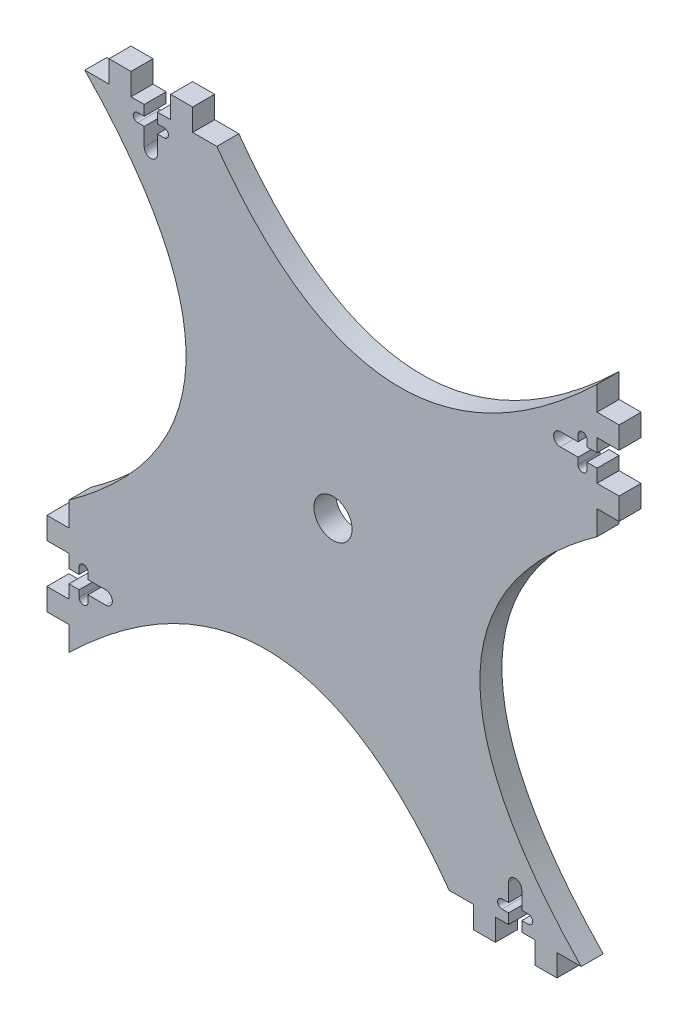
SolidWorks part; units mm, degrees
ref_plane "Front Plane" through (0, 0, 0) normal (0, 0, 1) x (1, 0, 0)
ref_plane "Top Plane" through (0, 0, 0) normal (0, 1, 0) x (1, 0, 0)
ref_plane "Right Plane" through (0, 0, 0) normal (1, 0, 0) x (0, 0, -1)
sketch "Sketch1" plane through (0, 0, 0) normal (0, 0, 1) x (1, 0, 0)
  line L0 (-16.6747, 52.5) -> (-46.6747, 52.5)
  line L1 (69.715, 48.8897) -> (69.715, 18.8897)
  line L2 (66.1047, -67.5) -> (36.1047, -67.5)
  line L3 (-50.285, -33.8897) -> (-50.285, -63.8897)
  line L9 (-31.6747, 52.5) -> (51.1047, -67.5) construction
  line L10 (-50.285, -48.8897) -> (69.715, 33.8897) construction
  circle A0 centre (9.715, -7.5) radius 35 construction
  circle A1 centre (9.715, -7.5) radius 4.337
  spline S0 degree 2 poles (69.715, 48.8897) (20.2003, 1.1367) (-16.6747, 52.5) knots 0 0 0 1 1 1
  spline S1 degree 2 poles (-46.6747, 52.5) (1.0783, 2.9853) (-50.285, -33.8897) knots 0 0 0 1 1 1
  spline S2 degree 2 poles (-50.285, -63.8897) (-0.7703, -16.1367) (36.1047, -67.5) knots 0 0 0 1 1 1
  spline S3 degree 2 poles (66.1047, -67.5) (18.3517, -17.9853) (69.715, 18.8897) knots 0 0 0 1 1 1
  dimension "D2" = 70
  dimension "D1" = 30
extrude "Boss-Extrude1" add sketch "Sketch1" along normal blind 5
sketch "Sketch2" plane through (0, 0, 5) normal (0, 0, 1) x (1, 0, 0)
  line L0 (-31.6747, 52.5) -> (-31.6747, 44.1355) construction
  line L1 (-16.6747, 52.5) -> (-46.6747, 52.5) construction
  line L2 (-33.1747, 52.5) -> (-33.1747, 44.1355)
  line L3 (-30.1747, 52.5) -> (-30.1747, 44.1355)
  line L4 (-34.6747, 49.181) -> (-28.6747, 49.181) construction
  line L5 (-34.6747, 50.181) -> (-28.6747, 50.181)
  line L6 (-34.6747, 48.181) -> (-28.6747, 48.181)
  line L23 (69.715, 35.3897) -> (61.3505, 35.3897)
  line L24 (69.715, 32.3897) -> (61.3505, 32.3897)
  line L25 (69.715, 33.8897) -> (61.3505, 33.8897) construction
  line L26 (66.396, 36.8897) -> (66.396, 30.8897) construction
  line L27 (69.715, 18.8897) -> (69.715, 48.8897)
  line L28 (36.1047, -67.5) -> (66.1047, -67.5)
  line L29 (-50.285, -33.8897) -> (-50.285, -63.8897)
  line L30 (-16.6747, 52.5) -> (-46.6747, 52.5)
  line L31 (69.715, 18.8897) -> (69.715, 48.8897)
  line L32 (36.1047, -67.5) -> (66.1047, -67.5)
  line L33 (-50.285, -33.8897) -> (-50.285, -63.8897)
  line L34 (-16.6747, 52.5) -> (-46.6747, 52.5)
  line L35 (69.715, 18.8897) -> (69.715, 48.8897)
  line L36 (36.1047, -67.5) -> (66.1047, -67.5)
  line L37 (-50.285, -33.8897) -> (-50.285, -63.8897)
  line L38 (-16.6747, 52.5) -> (-46.6747, 52.5)
  line L39 (69.715, 18.8897) -> (69.715, 48.8897)
  line L40 (36.1047, -67.5) -> (66.1047, -67.5)
  line L41 (-50.285, -33.8897) -> (-50.285, -63.8897)
  line L42 (-16.6747, 52.5) -> (-46.6747, 52.5)
  line L43 (67.396, 36.8897) -> (67.396, 30.8897)
  line L44 (65.396, 36.8897) -> (65.396, 30.8897)
  line L45 (52.6047, -67.5) -> (52.6047, -59.1355)
  line L46 (49.6047, -67.5) -> (49.6047, -59.1355)
  line L47 (51.1047, -67.5) -> (51.1047, -59.1355) construction
  line L48 (54.1047, -64.181) -> (48.1047, -64.181) construction
  line L49 (54.1047, -65.181) -> (48.1047, -65.181)
  line L50 (54.1047, -63.181) -> (48.1047, -63.181)
  line L51 (-50.285, -50.3897) -> (-41.9205, -50.3897)
  line L52 (-50.285, -47.3897) -> (-41.9205, -47.3897)
  line L53 (-50.285, -48.8897) -> (-41.9205, -48.8897) construction
  line L54 (-46.966, -51.8897) -> (-46.966, -45.8897) construction
  line L55 (-47.966, -51.8897) -> (-47.966, -45.8897)
  line L56 (-45.966, -51.8897) -> (-45.966, -45.8897)
  arc A0 (-33.1747, 52.5) -> (-30.1747, 52.5) centre (-31.6747, 52.5) cw
  arc A1 (-33.1747, 44.1355) -> (-30.1747, 44.1355) centre (-31.6747, 44.1355) ccw
  arc A2 (-34.6747, 50.181) -> (-34.6747, 48.181) centre (-34.6747, 49.181) ccw
  arc A3 (-28.6747, 48.181) -> (-28.6747, 50.181) centre (-28.6747, 49.181) ccw
  arc A4 (61.3505, 35.3897) -> (61.3505, 32.3897) centre (61.3505, 33.8897) ccw
  arc A5 (67.396, 36.8897) -> (65.396, 36.8897) centre (66.396, 36.8897) ccw
  arc A6 (65.396, 30.8897) -> (67.396, 30.8897) centre (66.396, 30.8897) ccw
  arc A7 (52.6047, -59.1355) -> (49.6047, -59.1355) centre (51.1047, -59.1355) ccw
  arc A8 (54.1047, -65.181) -> (54.1047, -63.181) centre (54.1047, -64.181) ccw
  arc A9 (48.1047, -63.181) -> (48.1047, -65.181) centre (48.1047, -64.181) ccw
  arc A10 (-41.9205, -50.3897) -> (-41.9205, -47.3897) centre (-41.9205, -48.8897) ccw
  arc A11 (-47.966, -51.8897) -> (-45.966, -51.8897) centre (-46.966, -51.8897) ccw
  arc A12 (-45.966, -45.8897) -> (-47.966, -45.8897) centre (-46.966, -45.8897) ccw
  parabola Q24 (66.1047, -67.5) -> (69.715, 18.8897) focus (61.8189, -20.3354) apex (43.3975, -17.9863)
  parabola Q25 (-50.285, -63.8897) -> (36.1047, -67.5) focus (-3.1204, -59.6039) apex (-0.7713, -41.1825)
  parabola Q26 (-46.6747, 52.5) -> (-50.285, -33.8897) focus (-42.3889, 5.3354) apex (-23.9675, 2.9863)
  parabola Q27 (69.715, 48.8897) -> (-16.6747, 52.5) focus (22.5504, 44.6039) apex (20.2013, 26.1825)
  parabola Q28 (66.1047, -67.5) -> (69.715, 18.8897) focus (61.8189, -20.3354) apex (43.3975, -17.9863)
  parabola Q29 (-50.285, -63.8897) -> (36.1047, -67.5) focus (-3.1204, -59.6039) apex (-0.7713, -41.1825)
  parabola Q30 (-46.6747, 52.5) -> (-50.285, -33.8897) focus (-42.3889, 5.3354) apex (-23.9675, 2.9863)
  parabola Q31 (69.715, 48.8897) -> (-16.6747, 52.5) focus (22.5504, 44.6039) apex (20.2013, 26.1825)
  parabola Q32 (66.1047, -67.5) -> (69.715, 18.8897) focus (61.8189, -20.3354) apex (43.3975, -17.9863)
  parabola Q33 (-50.285, -63.8897) -> (36.1047, -67.5) focus (-3.1204, -59.6039) apex (-0.7713, -41.1825)
  parabola Q34 (-46.6747, 52.5) -> (-50.285, -33.8897) focus (-42.3889, 5.3354) apex (-23.9675, 2.9863)
  parabola Q35 (69.715, 48.8897) -> (-16.6747, 52.5) focus (22.5504, 44.6039) apex (20.2013, 26.1825)
  parabola Q36 (66.1047, -67.5) -> (69.715, 18.8897) focus (61.8189, -20.3354) apex (43.3975, -17.9863)
  parabola Q37 (-50.285, -63.8897) -> (36.1047, -67.5) focus (-3.1204, -59.6039) apex (-0.7713, -41.1825)
  parabola Q38 (-46.6747, 52.5) -> (-50.285, -33.8897) focus (-42.3889, 5.3354) apex (-23.9675, 2.9863)
  parabola Q39 (69.715, 48.8897) -> (-16.6747, 52.5) focus (22.5504, 44.6039) apex (20.2013, 26.1825)
  point P10 (-31.6747, 49.181)
  point P52 (66.396, 33.8897)
  point P65 (51.1047, -64.181)
  point P92 (-46.966, -48.8897)
  spline M17 degree 2 poles (69.715, 48.8897) (20.2003, 1.1367) (-16.6747, 52.5) knots 0 0 0 1 1 1
  line M18 (-16.6747, 52.5) -> (-46.6747, 52.5)
  spline M21 degree 2 poles (-50.285, -63.8897) (-0.7703, -16.1367) (36.1047, -67.5) knots 0 0 0 1 1 1
  line M22 (36.1047, -67.5) -> (66.1047, -67.5)
  spline M23 degree 2 poles (66.1047, -67.5) (18.3517, -17.9853) (69.715, 18.8897) knots 0 0 0 1 1 1
  line M24 (69.715, 18.8897) -> (69.715, 48.8897)
  dimension "D3" = 2
  dimension "D4" = 8
  dimension "D1" = 1.5
  dimension "D2" = 1.5
  dimension "D5" = 0
  dimension "D6" = 0
  dimension "D7" = 4
extrude "Cut-Extrude1" cut sketch "Sketch2" against normal blind 10 flip side to cut contours A12 L56 L52 A10 L51 A11 L55 L41 L46 L49 A9 L50 A7 L45 A8 L40 L24 L43 A6 L44 A4 L23 A5 L3 L5 A3 L6 A1 L2 A2 M21 M22 M23 M24 M17 M18 region at (9.715, -7.5, 5)
sketch "Sketch3" plane through (0, 0, 5) normal (0, 0, 1) x (1, 0, 0)
  line L0 (-33.1747, 52.5) -> (-46.6747, 52.5) construction
  line L1 (-36.1747, 52.5) -> (-41.1747, 52.5)
  line L2 (-36.1747, 52.5) -> (-36.1747, 57.5)
  line L3 (-36.1747, 57.5) -> (-41.1747, 57.5)
  line L4 (-41.1747, 52.5) -> (-41.1747, 57.5)
  line L5 (-16.6747, 52.5) -> (-30.1747, 52.5) construction
  line L6 (-27.1747, 52.5) -> (-22.1747, 52.5)
  line L7 (-27.1747, 52.5) -> (-27.1747, 57.5)
  line L8 (-27.1747, 57.5) -> (-22.1747, 57.5)
  line L9 (-22.1747, 52.5) -> (-22.1747, 57.5)
  line L10 (-33.1747, 52.5) -> (-33.1747, 50.181) construction
  line L11 (-30.1747, 52.5) -> (-30.1747, 50.181) construction
  line L12 (69.715, 38.3897) -> (69.715, 43.3897)
  line L13 (69.715, 38.3897) -> (74.715, 38.3897)
  line L14 (74.715, 38.3897) -> (74.715, 43.3897)
  line L15 (69.715, 43.3897) -> (74.715, 43.3897)
  line L16 (69.715, 29.3897) -> (69.715, 24.3897)
  line L17 (69.715, 29.3897) -> (74.715, 29.3897)
  line L18 (74.715, 29.3897) -> (74.715, 24.3897)
  line L19 (69.715, 24.3897) -> (74.715, 24.3897)
  line L20 (55.6047, -67.5) -> (60.6047, -67.5)
  line L21 (55.6047, -67.5) -> (55.6047, -72.5)
  line L22 (55.6047, -72.5) -> (60.6047, -72.5)
  line L23 (60.6047, -67.5) -> (60.6047, -72.5)
  line L24 (46.6047, -67.5) -> (41.6047, -67.5)
  line L25 (46.6047, -67.5) -> (46.6047, -72.5)
  line L26 (46.6047, -72.5) -> (41.6047, -72.5)
  line L27 (41.6047, -67.5) -> (41.6047, -72.5)
  line L28 (-50.285, -53.3897) -> (-50.285, -58.3897)
  line L29 (-50.285, -53.3897) -> (-55.285, -53.3897)
  line L30 (-55.285, -53.3897) -> (-55.285, -58.3897)
  line L31 (-50.285, -58.3897) -> (-55.285, -58.3897)
  line L32 (-50.285, -44.3897) -> (-50.285, -39.3897)
  line L33 (-50.285, -44.3897) -> (-55.285, -44.3897)
  line L34 (-55.285, -44.3897) -> (-55.285, -39.3897)
  line L35 (-50.285, -39.3897) -> (-55.285, -39.3897)
  dimension "D1" = 5
  dimension "D2" = 3
  dimension "D3" = 5
  dimension "D4" = 3
  dimension "D5" = 5
  dimension "D6" = 4
extrude "Boss-Extrude2" add sketch "Sketch3" against normal blind 5
